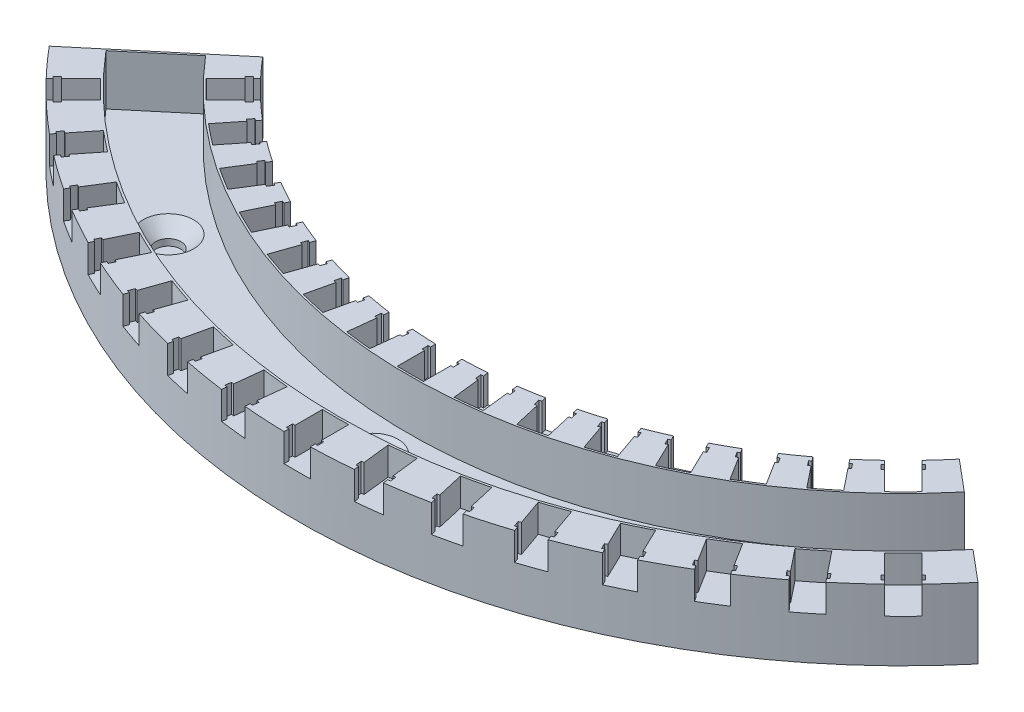
SolidWorks part; units mm, degrees
ref_plane "Front Plane" through (0, 0, 0) normal (0, 0, 1) x (1, 0, 0)
ref_plane "Top Plane" through (0, 0, 0) normal (0, 1, 0) x (1, 0, 0)
ref_plane "Right Plane" through (0, 0, 0) normal (1, 0, 0) x (0, 0, -1)
sketch "Sketch1" plane through (0, 0, 0) normal (0, 1, 0) x (1, 0, 0)
  line L0 (0, -90) -> (0, -120) construction
  line L1 (-68.944, -57.8509) -> (-91.9253, -77.1345)
  line L2 (68.944, -57.8509) -> (91.9253, -77.1345)
  arc A0 (-85.797, -71.9922) -> (85.797, -71.9922) centre (0, 0) ccw
  arc A1 (-91.9253, -77.1345) -> (91.9253, -77.1345) centre (0, 0) ccw
  arc A2 (75.0724, -62.9932) -> (-75.0724, -62.9932) centre (0, 0) cw
  arc A3 (-68.944, -57.8509) -> (68.944, -57.8509) centre (0, 0) ccw
  dimension "D6" = 120
  dimension "D2" = 50
  dimension "D3" = 50
  dimension "D1" = 14
  dimension "D4" = 8
  dimension "D5" = 8
extrude "Boss-Extrude1" add sketch "Sketch1" against normal blind 4 contours A3 L0 A2 L2 | L0 A3 L1 A2 | L0 A2 L1 A0 | L0 A0 L1 A1 | A2 L0 A0 L2 | A0 L0 A1 L2 region at (38.5007, 0, 82.5651) region at (-38.5007, 0, 82.5651) region at (43.0439, 0, 92.3079) region at (-43.0439, 0, 92.3079) region at (47.5017, 0, 101.8677) region at (-47.5017, 0, 101.8677)
extrude "Boss-Extrude2" add sketch "Sketch1<3>" along normal blind 10 contours L0 A3 L1 A2 | A3 L0 A2 L2 | A0 L0 A1 L2 | L0 A0 L1 A1 region at (38.5007, 0, 82.5651) region at (-38.5007, 0, 82.5651) region at (47.5017, 0, 101.8677) region at (-47.5017, 0, 101.8677)
sketch "Sketch1<3>" plane through (0, 0, 0) normal (0, 1, 0) x (1, 0, 0) same geometry as "Sketch1"
sketch "Sketch2" plane through (0, 10, 0) normal (0, 1, 0) x (1, 0, 0)
  line L1 (-2.6, -120) -> (2.6, -120)
  line L2 (-2.6, -120) -> (-2.6, -111.9698)
  line L3 (-2.6, -111.9698) -> (2.6, -111.9698)
  line L4 (2.6, -120) -> (2.6, -111.9698)
  line L5 (-2.6, -120) -> (2.6, -111.9698) construction
  line L6 (-2.6, -111.9698) -> (2.6, -120) construction
  line L7 (-3.1, -119) -> (3.1, -119)
  line L8 (-3.1, -119) -> (-3.1, -117.8)
  line L9 (-3.1, -117.8) -> (3.1, -117.8)
  line L10 (3.1, -119) -> (3.1, -117.8)
  line L11 (-3.1, -119) -> (3.1, -117.8) construction
  line L12 (-3.1, -117.8) -> (3.1, -119) construction
  line L13 (-2.6, -98) -> (2.6, -98)
  line L14 (-2.6, -98) -> (-2.6, -89.9624)
  line L15 (-2.6, -89.9624) -> (2.6, -89.9624)
  line L16 (2.6, -98) -> (2.6, -89.9624)
  line L17 (-2.6, -98) -> (2.6, -89.9624) construction
  line L18 (-2.6, -89.9624) -> (2.6, -98) construction
  line L19 (-3.1, -90.9624) -> (3.1, -90.9624)
  line L20 (-3.1, -90.9624) -> (-3.1, -92.1624)
  line L21 (-3.1, -92.1624) -> (3.1, -92.1624)
  line L22 (3.1, -90.9624) -> (3.1, -92.1624)
  line L23 (-3.1, -90.9624) -> (3.1, -92.1624) construction
  line L24 (-3.1, -92.1624) -> (3.1, -90.9624) construction
  arc A0 (-91.9253, -77.1345) -> (91.9253, -77.1345) centre (0, 0) ccw construction
  arc A1 (-85.797, -71.9922) -> (85.797, -71.9922) centre (0, 0) ccw construction
  arc A2 (-68.944, -57.8509) -> (68.944, -57.8509) centre (0, 0) ccw construction
  arc A3 (-75.0724, -62.9932) -> (75.0724, -62.9932) centre (0, 0) ccw construction
  point P0 (0, -115.9849)
  point P5 (0, -118.4)
  point P18 (0, -93.9812)
  point P28 (0, -91.5624)
  arc M8 (85.797, -71.9922) -> (-85.797, -71.9922) centre (0, 0) cw
  arc M10 (-91.9253, -77.1345) -> (91.9253, -77.1345) centre (0, 0) ccw
  dimension "D1" = 5.2
  dimension "D2" = 6.2
  dimension "D3" = 1.2
  dimension "D4" = 1
  dimension "D5" = 1
ref_plane "Plane1" through (0, 7, 0) normal (0, 1, 0) x (1, 0, 0)
extrude "Cut-Extrude1" cut sketch "Sketch2" against normal offset from surface (5.5 mm away) 2.5 contours L2 L9 L4 M8 | L9 L2 L7 L4 | L7 L10 L9 L4 | L9 L8 L7 L2 | L7 L2 L4 M10 | L21 L14 L13 L16 | L14 L21 L16 L19 | L20 L21 L14 L19 | L14 L19 L16 L15 | L22 L19 L16 L21 region at (0, 10, 119.4953) region at (-2.85, 10, 118.4) region at (0, 10, 118.4) region at (2.85, 10, 118.4) region at (0, 10, 114.895) region at (0, 10, 95.0812) region at (-2.85, 10, 91.5624) region at (0, 10, 91.5624) region at (2.85, 10, 91.5624) region at (0, 10, 90.4624) up to plane "Plane1" offset beyond the face yes
ref_axis "Axis1" through (0, 10.7, 0) along (0, -1, 0)
pattern_circular "CirPattern1" count 8 every 6.429 about axis through (0, 10.7, 0) along (0, -1, 0) of "Cut-Extrude1" other way count 8
sketch "Sketch3" plane through (0, 0, 0) normal (0, 1, 0) x (1, 0, 0)
  line L0 (75.0724, -62.9932) -> (85.797, -71.9922) construction
  line L1 (-68.944, -57.8509) -> (-75.0724, -62.9932) construction
  line L2 (68.944, -57.8509) -> (75.0724, -62.9932) construction
  line L3 (-75.0724, -62.9932) -> (-85.797, -71.9922) construction
  line L4 (85.797, -71.9922) -> (91.9253, -77.1345) construction
  line L5 (-85.797, -71.9922) -> (-91.9253, -77.1345) construction
  line L6 (74.7659, -62.7361) -> (75.0724, -62.9932)
  line L7 (85.797, -71.9922) -> (86.1034, -72.2493)
  line L8 (-86.1034, -72.2493) -> (-85.797, -71.9922)
  line L9 (-75.0724, -62.9932) -> (-74.7659, -62.7361)
  line L10 (-75.0724, -62.9932) -> (-85.797, -71.9922)
  line L11 (-74.8146, -63.2991) -> (-85.5393, -72.2982)
  arc A0 (-75.0724, -62.9932) -> (75.0724, -62.9932) centre (0, 0) ccw
  arc A1 (-74.7659, -62.7361) -> (74.7659, -62.7361) centre (0, 0) ccw
  arc A2 (85.797, -71.9922) -> (-85.797, -71.9922) centre (0, 0) cw
  arc A3 (86.1034, -72.2493) -> (-86.1034, -72.2493) centre (0, 0) cw
  arc M1 (-85.797, -71.9922) -> (85.797, -71.9922) centre (0, 0) ccw
  arc M3 (75.0724, -62.9932) -> (-75.0724, -62.9932) centre (0, 0) cw
  line M4 (-75.0724, -62.9932) -> (-85.797, -71.9922)
  dimension "D1" = 0.4
  dimension "D2" = 0.4
  dimension "D3" = 0.4
extrude "Boss-Extrude3" add sketch "Sketch3" along normal up to surface (10 mm away) contours L11 M3 M4 M1 | A1 L9 L6 M3 | A3 L7 L8 M1 region at (73.9278, 0, 64.0461) region at (-80.3059, 0, 67.6457) region at (0.2003, 0, 112.1767) up to face at (-5.1797, 10, 92.2338)
sketch "Sketch4" plane through (0, 0, 0) normal (0, 1, 0) x (1, 0, 0)
  line L0 (-75.0724, -62.9932) -> (-85.797, -71.9922) construction
  circle A0 centre (0, 0) radius 105 construction
  circle A1 centre (0, -105) radius 2.5
  circle A2 centre (57.8812, -87.6058) radius 2.5
  circle A3 centre (-57.8812, -87.6058) radius 2.5
  circle A4 centre (-57.8812, -87.6058) radius 30.2191 construction
  circle A5 centre (0, -105) radius 30.2191 construction
  circle A6 centre (57.8812, -87.6058) radius 30.2191 construction
  point P5 (-80.4347, -67.4927)
  dimension "D1" = 5
extrude "Cut-Extrude2" cut sketch "Sketch4" against normal offset from surface (3.8 mm away) 0.2 up to face at (0, -4, 86.2463)
chamfer "Chamfer1" distance 2.5 angle 45 3 edges at (57.8812, 0, 90.1058) (0, 0, 107.5) (-57.8812, 0, 90.1058)
equation "\"D3@Sketch1\"=\"D2@Sketch1\""
equation "\"D5@Sketch2\"=\"D4@Sketch2\""
equation "\"D2@Sketch3\"=\"D1@Sketch3\""
equation "\"D3@Sketch3\"=\"D1@Sketch3\""
